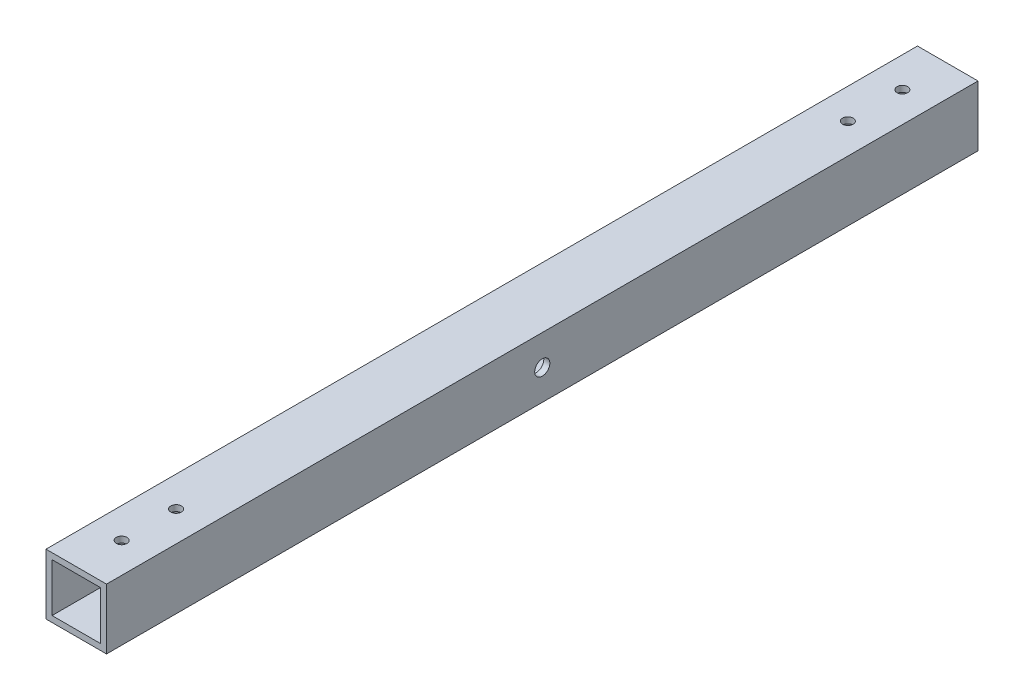
SolidWorks part; units mm, degrees
ref_plane "Front Plane" through (0, 0, 0) normal (0, 0, 1) x (1, 0, 0)
ref_plane "Top Plane" through (0, 0, 0) normal (0, 1, 0) x (1, 0, 0)
ref_plane "Right Plane" through (0, 0, 0) normal (1, 0, 0) x (0, 0, -1)
sketch "Sketch1" plane through (0, 0, 0) normal (0, 0, 1) x (1, 0, 0)
  line L0 (31.75, 0) -> (25.4, 0) construction
  line L1 (-31.75, 0) -> (31.75, 0) construction
  line L2 (0, 31.75) -> (0, -31.75)
  point P7 (0, 0)
sketch "Sketch2" plane through (0, 0, 0) normal (1, 0, 0) x (0, 0, -1)
  line L0 (457.2, 0) -> (-457.2, 0)
  point P4 (0, 0)
  dimension "Length" = 914.4
sketch "Sketch3" plane through (0, 0, 0) normal (0, 0, 1) x (1, 0, 0)
  line L0 (-31.75, 0) -> (31.75, 0) construction
  line L5 (31.75, -31.75) -> (-31.75, -31.75)
  line L6 (31.75, -31.75) -> (31.75, 31.75)
  line L11 (31.75, 31.75) -> (-31.75, 31.75)
  line L12 (-31.75, -31.75) -> (-31.75, 31.75)
  line L14 (31.75, -31.75) -> (-31.75, 31.75) construction
  line L15 (31.75, 31.75) -> (-31.75, -31.75) construction
  line L16 (25.4, -25.4) -> (-25.4, -25.4)
  line L17 (25.4, -25.4) -> (25.4, 25.4)
  line L18 (25.4, 25.4) -> (-25.4, 25.4)
  line L19 (-25.4, -25.4) -> (-25.4, 25.4)
  line L20 (25.4, -25.4) -> (-25.4, 25.4) construction
  line L21 (25.4, 25.4) -> (-25.4, -25.4) construction
  point P0 (0, 0)
  point P5 (0, 0)
  point P13 (25.4, -31.75)
  dimension "D1" = 6.35
  dimension "D3" = 63.5
  dimension "D4" = 63.5
  dimension "D2" = 6.35
extrude "Boss-Extrude1" add sketch "Sketch3" along normal up to vertex (457.2 mm away) and the other way up to vertex (457.2 mm away) up to point (0, 0, 457.2) other way up to point (0, 0, -457.2)
sketch "Sketch5" plane through (0, 0, 0) normal (1, 0, 0) x (0, 0, -1)
  line L0 (-457.2, 0) -> (457.2, 0) construction
  line L3 (-457.2, -31.75) -> (-457.2, 31.75) construction
  line L4 (457.2, -31.75) -> (457.2, 31.75) construction
  point P6 (-385.7625, 0)
  point P7 (-361.95, 0)
  point P8 (361.95, 0)
  point P10 (385.7625, 0)
  dimension "D1" = 71.4375
  dimension "D2" = 95.25
  dimension "D3" = 71.4375
  dimension "D4" = 95.25
sketch "Sketch6" plane through (0, 31.75, 0) normal (0, 1, 0) x (1, 0, 0)
  line L0 (0, 457.2) -> (0, 388.9644) construction
  line L1 (31.75, 457.2) -> (-31.75, 457.2) construction
  line L2 (31.75, -457.2) -> (-31.75, -457.2) construction
  line L3 (0, -457.2) -> (0, -352.425) construction
  circle A0 centre (0, 409.575) radius 5.588
  circle A1 centre (0, -409.575) radius 5.588
  circle A2 centre (0, -352.425) radius 5.588
  circle A3 centre (0, 352.425) radius 5.588
  dimension "D5" = 11.176
  dimension "D6" = 11.176
  dimension "D7" = 11.176
  dimension "D8" = 11.176
  dimension "D1" = 47.625
  dimension "D2" = 47.625
  dimension "D3" = 57.15
  dimension "D4" = 57.15
extrude "Cut-Extrude1" cut sketch "Sketch6" against normal through all
sketch "Sketch7" plane through (31.75, 0, 0) normal (1, 0, 0) x (0, 0, -1)
  line L1 (-457.2, -31.75) -> (457.2, -31.75) construction
  line L2 (-457.2, -31.75) -> (-457.2, 31.75) construction
  line L3 (-457.2, 31.75) -> (457.2, 31.75) construction
  line L4 (457.2, -31.75) -> (457.2, 31.75) construction
  line L5 (-457.2, -31.75) -> (457.2, 31.75) construction
  line L6 (-457.2, 31.75) -> (457.2, -31.75) construction
  circle A0 centre (0, 0) radius 7.9375
  point P0 (0, 0)
  dimension "D1" = 15.875
extrude "Cut-Extrude2" cut sketch "Sketch7" against normal through all
sketch "Sketch9" plane through (0, 31.75, 0) normal (0, 1, 0) x (1, 0, 0)
  line L0 (0, 0) -> (0, 304.8)
  point P5 (0, 304.8)
  dimension "D1" = 304.8
equation "\"D1@Sketch3\"=\"Wall thickness@Sketch1\""
equation "\"D1@Sketch5\"=\"Width@Sketch1\"*1.125"
equation "\"D2@Sketch5\"=\"Width@Sketch1\"*1.5"
equation "\"D3@Sketch5\"=\"D1@Sketch5\""
equation "\"D4@Sketch5\"=\"D2@Sketch5\""
equation "\"D2@Sketch3\"=\"Wall Thickness@Sketch1\""
